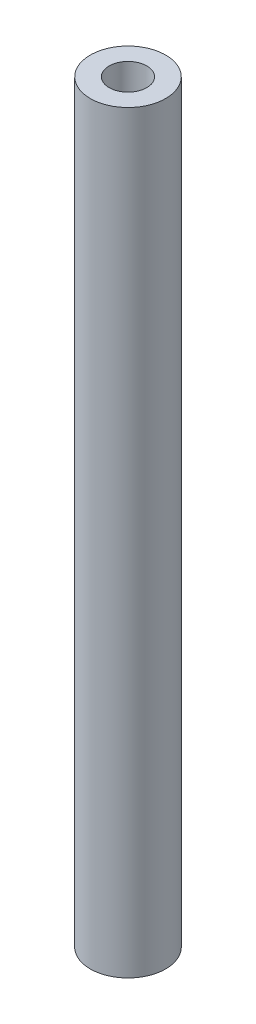
SolidWorks part; units mm, degrees
ref_plane "前视基准面" through (0, 0, 0) normal (0, 0, 1) x (1, 0, 0)
ref_plane "上视基准面" through (0, 0, 0) normal (0, 1, 0) x (1, 0, 0)
ref_plane "右视基准面" through (0, 0, 0) normal (1, 0, 0) x (0, 0, -1)
sketch "草图1" plane through (0, 0, 0) normal (0, 1, 0) x (1, 0, 0)
  circle A1 centre (0, 0) radius 2.5
  dimension "D1" = 5
extrude "凸台-拉伸1" add sketch "草图1" along normal blind 50
sketch "草图4" plane through (0, 50, 0) normal (0, 1, 0) x (1, 0, 0)
  point P0 (0, 0)
hole_wizard "M3 螺纹孔1" positions "草图4" profile "草图3" tap size "M3" standard "GB" end condition through all
sketch "草图3" plane through (0, 50, 0) normal (1, 0, 0) x (0, 0, 1)
  line L0 (0, 0) -> (0, 50)
  line L1 (0, 50) -> (1.25, 50)
  line L2 (1.25, 50) -> (1.25, 0)
  line L5 (1.25, 0) -> (0, 0)
  line L11 (0, -6.35) -> (0, 107.95) construction
  dimension "通孔螺纹孔钻头直径" = 2.5
  dimension "通孔螺纹孔钻头深度" = 50
